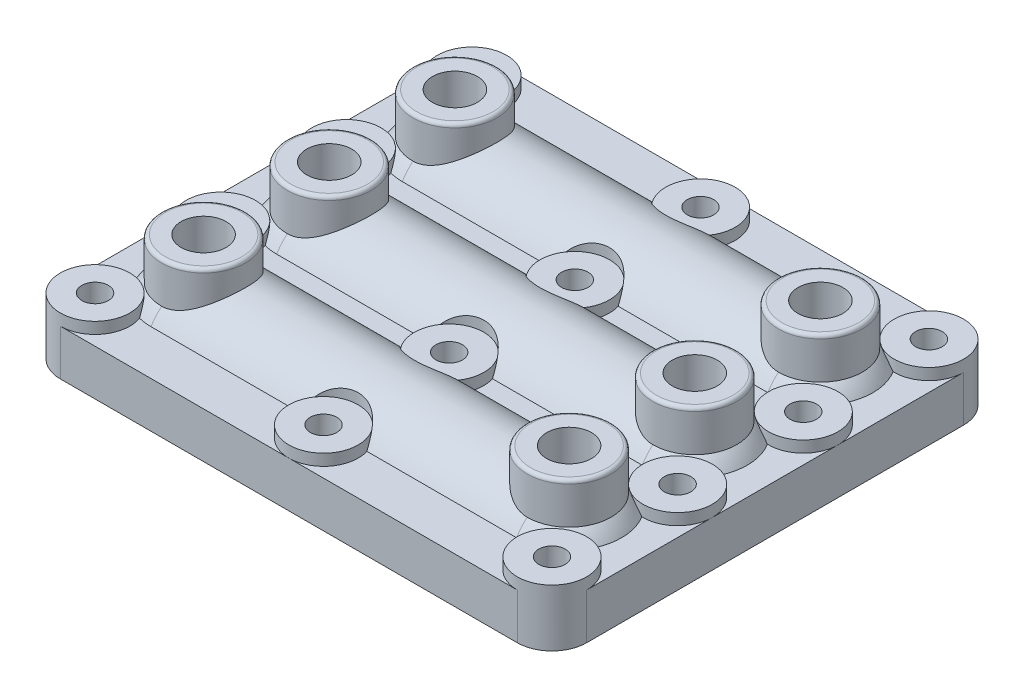
SolidWorks part; units mm, degrees
ref_plane "Front" through (0, 0, 0) normal (0, 0, 1) x (1, 0, 0)
ref_plane "Top" through (0, 0, 0) normal (0, 1, 0) x (1, 0, 0)
ref_plane "Right" through (0, 0, 0) normal (1, 0, 0) x (0, 0, -1)
sketch "Hole Layout" plane through (0, 0, 0) normal (0, 1, 0) x (1, 0, 0)
  line L0 (-31.75, 8.7312) -> (31.75, 8.7312) construction
  line L1 (0, 26.1937) -> (0, -26.1937) construction
  line L2 (-31.75, 26.1937) -> (31.75, 26.1937) construction
  line L3 (-31.75, -8.7313) -> (31.75, -8.7312) construction
  line L4 (-31.75, -26.1937) -> (31.75, -26.1937) construction
  circle A0 centre (-31.75, 26.1937) radius 3.175
  circle A1 centre (0, 26.1937) radius 3.175
  circle A2 centre (31.75, 26.1937) radius 3.175
  circle A3 centre (-31.75, 8.7312) radius 3.175
  circle A4 centre (0, 8.7312) radius 3.175
  circle A5 centre (31.75, 8.7312) radius 3.175
  circle A6 centre (-31.75, -8.7313) radius 3.175
  circle A7 centre (0, -8.7312) radius 3.175
  circle A8 centre (31.75, -8.7312) radius 3.175
  circle A9 centre (-31.75, -26.1937) radius 3.175
  circle A10 centre (0, -26.1937) radius 3.175
  circle A11 centre (31.75, -26.1937) radius 3.175
  circle A12 centre (-31.75, 26.1937) radius 2.413
  point P5 (0, 0)
  point P8 (0, 26.1937)
  point P10 (0, 8.7312)
  point P11 (0, -8.7312)
  dimension "D8" = 6.35
  dimension "D9" = 6.35
  dimension "D10" = 6.35
  dimension "D11" = 6.35
  dimension "D12" = 6.35
  dimension "D13" = 6.35
  dimension "D14" = 6.35
  dimension "D15" = 6.35
  dimension "D16" = 6.35
  dimension "D17" = 6.35
  dimension "D18" = 6.35
  dimension "D19" = 6.35
  dimension "D20" = 4.826
  dimension "D1" = 63.5
  dimension "D2" = 52.3875
  dimension "D3" = 63.5
  dimension "D4" = 8.7312
  dimension "D5" = 63.5
  dimension "D6" = 8.7312
  dimension "D7" = 63.5
sketch "Gas Layout" plane through (0, 0, 0) normal (0, 1, 0) x (1, 0, 0)
  line L0 (-25.4, 0) -> (25.4, 0) construction
  line L1 (-25.4, 17.4625) -> (25.4, 17.4625) construction
  line L2 (-25.4, -17.4625) -> (25.4, -17.4625) construction
  line L3 (0, 17.4625) -> (0, -17.4625) construction
  circle A0 centre (-25.4, 17.4625) radius 1.5875
  circle A1 centre (-25.4, 0) radius 1.5875
  circle A2 centre (-25.4, -17.4625) radius 1.5875
  circle A3 centre (25.4, 17.4625) radius 1.5875
  circle A4 centre (25.4, 0) radius 1.5875
  circle A5 centre (25.4, -17.4625) radius 1.5875
  point P5 (0, 17.4625)
  point P18 (0, 0)
  point P19 (0, -17.4625)
  dimension "D4" = 3.175
  dimension "D5" = 3.175
  dimension "D6" = 3.175
  dimension "D7" = 3.175
  dimension "D8" = 3.175
  dimension "D9" = 3.175
  dimension "D1" = 50.8
  dimension "D2" = 50.8
  dimension "D3" = 50.8
  dimension "D10" = 34.925
sketch "Gas Channel" plane through (0, 0, 0) normal (0, 1, 0) x (1, 0, 0)
  line L0 (-19.05, 17.4625) -> (19.05, 17.4625) construction
  line L1 (19.05, 15.2174) -> (19.05, 19.7076) construction
  line L2 (-25.4, 17.4625) -> (25.4, 17.4625) construction
  line L3 (-19.05, 19.7076) -> (19.05, 19.7076)
  line L4 (-19.05, 15.2174) -> (19.05, 15.2174)
  arc A0 (-19.05, 19.7076) -> (-19.05, 15.2174) centre (-19.05, 17.4625) ccw
  arc A1 (19.05, 15.2174) -> (19.05, 19.7076) centre (19.05, 17.4625) ccw
  point P5 (0, 17.4625)
  dimension "D1" = 19.05
  dimension "D2" = 4.4901
sketch "Perimeter" plane through (0, 0, 0) normal (0, 1, 0) x (1, 0, 0)
  line L0 (-31.75, 31.0197) -> (31.75, 31.0197)
  line L1 (-36.576, 26.1937) -> (-36.576, -26.1937)
  line L2 (36.576, 26.1937) -> (36.576, -26.1937)
  line L3 (-31.75, -31.0197) -> (31.75, -31.0197)
  circle A0 centre (-31.75, 26.1937) radius 4.826
  circle A1 centre (31.75, 26.1937) radius 4.826
  circle A2 centre (-31.75, -26.1937) radius 4.826
  circle A3 centre (31.75, -26.1937) radius 4.826
  dimension "D1" = 9.652
  dimension "D2" = 9.652
  dimension "D3" = 9.652
  dimension "D4" = 9.652
sketch "Footprint A" plane through (0, 0, 0) normal (0, 1, 0) x (1, 0, 0)
  line L0 (-31.75, 8.7312) -> (31.75, 8.7312) construction
  circle A0 centre (-31.75, 26.1937) radius 3.302
  circle A1 centre (0, 26.1937) radius 3.302
  circle A2 centre (31.75, 26.1937) radius 3.302
  circle A3 centre (-31.75, 8.7312) radius 3.302
  circle A4 centre (0, 8.7312) radius 3.302
  circle A5 centre (31.75, 8.7312) radius 3.302
  circle A6 centre (-31.75, -8.7313) radius 3.302
  circle A7 centre (0, -8.7312) radius 3.302
  circle A8 centre (31.75, -8.7312) radius 3.302
  circle A9 centre (-31.75, -26.1937) radius 3.302
  circle A10 centre (0, -26.1937) radius 3.302
  circle A11 centre (31.75, -26.1937) radius 3.302
  dimension "D1" = 6.604
  dimension "D2" = 6.604
  dimension "D3" = 6.604
  dimension "D4" = 6.604
  dimension "D5" = 6.604
  dimension "D6" = 6.604
  dimension "D7" = 6.604
  dimension "D8" = 6.604
  dimension "D9" = 6.604
  dimension "D10" = 6.604
  dimension "D11" = 6.604
  dimension "D12" = 6.604
sketch "Footprint B" plane through (0, 0, 0) normal (0, 1, 0) x (1, 0, 0)
  line L0 (-31.75, 31.0197) -> (31.75, 31.0197)
  line L1 (-36.576, 26.1937) -> (-36.576, -26.1937)
  line L2 (36.576, 26.1937) -> (36.576, -26.1937)
  line L3 (-31.75, -31.0197) -> (31.75, -31.0197)
  arc A0 (-31.75, 31.0197) -> (-36.576, 26.1937) centre (-31.75, 26.1937) ccw
  arc A6 (36.576, 26.1937) -> (31.75, 31.0197) centre (31.75, 26.1937) ccw
  arc A12 (-36.576, -26.1937) -> (-31.75, -31.0197) centre (-31.75, -26.1937) ccw
  arc A13 (31.75, -31.0197) -> (36.576, -26.1937) centre (31.75, -26.1937) ccw
  dimension "D1" = 9.652
  dimension "D2" = 9.652
  dimension "D3" = 9.652
extrude "Boss-Extrude1" add sketch "Footprint B" along normal blind 1.5875 contours L3 A13 L2 A6 L0 A0 L1 A12 region at (0, 0, 0)
ref_plane "Plane3" through (0, 1.5875, 0) normal (0, 1, 0) x (1, 0, 0)
sketch "Main Body A" plane through (0, 1.5875, 0) normal (0, 1, 0) x (1, 0, 0)
  line L0 (-36.576, 26.1937) -> (-36.576, -26.1937)
  line L1 (-31.75, -31.0197) -> (31.75, -31.0197)
  line L2 (36.576, -26.1937) -> (36.576, 26.1937)
  line L3 (31.75, 31.0198) -> (-31.75, 31.0197)
  line L4 (-31.75, 31.0197) -> (31.75, 31.0197) construction
  line L5 (-31.75, -31.0197) -> (31.75, -31.0197) construction
  line L6 (36.576, 26.1937) -> (36.576, -26.1937) construction
  line L7 (-36.576, 26.1937) -> (-36.576, -26.1937) construction
  arc A0 (-36.576, -26.1937) -> (-31.75, -31.0197) centre (-31.75, -26.1937) ccw
  arc A1 (31.75, -31.0197) -> (36.576, -26.1937) centre (31.75, -26.1937) ccw
  arc A2 (36.576, 26.1937) -> (31.75, 31.0198) centre (31.75, 26.1937) ccw
  arc A3 (-36.576, 26.1937) -> (-31.75, 31.0197) centre (-31.75, 26.1937) cw
  dimension "D1" = 4.826
extrude "Boss-Extrude2" add sketch "Main Body A" along normal blind 4.7625
sketch "Inlet/outlet posts" plane through (0, 0, 0) normal (0, 1, 0) x (1, 0, 0)
  circle A0 centre (25.4, 17.4625) radius 5.842
  circle A2 centre (25.4, 0) radius 5.842
  circle A3 centre (25.4, -17.4625) radius 5.842
  circle A4 centre (-25.4, -17.4625) radius 5.842
  circle A5 centre (-25.4, 0) radius 5.842
  circle A6 centre (-25.4, 17.4625) radius 5.842
  dimension "D1" = 11.684
  dimension "D2" = 11.684
  dimension "D3" = 11.684
  dimension "D4" = 11.684
  dimension "D5" = 11.684
  dimension "D6" = 11.684
extrude "Boss-Extrude4" add sketch "Inlet/outlet posts" along normal blind 13.7795
sketch "Sketch21" plane through (0, 1.5875, 0) normal (0, 1, 0) x (-1, 0, 0)
  line L0 (-41.0473, -17.4625) -> (41.0473, -17.4625) construction
  line L1 (0, -17.4625) -> (0, 0) construction
  line L2 (25.4, -17.4625) -> (-25.4, -17.4625) construction
  line L3 (25.4, -17.4625) -> (-25.4, -17.4625) construction
  line L5 (25.4, -8.7312) -> (-25.4, -8.7313)
  line L6 (34.1313, -17.4625) -> (-34.1313, -17.4625)
  arc A0 (34.1313, -17.4625) -> (25.4, -8.7312) centre (25.4, -17.4625) ccw
  arc A1 (-25.4, -8.7313) -> (-34.1313, -17.4625) centre (-25.4, -17.4625) ccw
  point P9 (0, -17.4625)
  point P12 (0, -17.4625)
  point P18 (0, -8.7312)
  point P19 (0, -8.7312)
revolve "Revolve2" add sketch "Sketch21" angle 180 about L0
pattern_linear "LPattern1" count 3 spacing 17.4625 along (0, 0, 1) of "Revolve2"
sketch "Sketch22" plane through (0, 6.35, 0) normal (0, 1, 0) x (1, 0, 0)
  circle A0 centre (-31.75, 26.1937) radius 4.826
  circle A1 centre (-31.75, 8.7312) radius 4.826
  circle A2 centre (-31.75, -8.7313) radius 4.826
  circle A3 centre (-31.75, -26.1937) radius 4.826
  circle A4 centre (0, -26.1938) radius 4.826
  circle A5 centre (0, -8.7312) radius 4.826
  circle A6 centre (0, 8.7312) radius 4.826
  circle A7 centre (0, 26.1937) radius 4.826
  circle A8 centre (31.75, 26.1937) radius 4.826
  circle A9 centre (31.75, 8.7312) radius 4.826
  circle A10 centre (31.75, -8.7312) radius 4.826
  circle A11 centre (31.75, -26.1937) radius 4.826
  dimension "D1" = 9.652
extrude "Boss-Extrude5" add sketch "Sketch22" along normal blind 1.5875
sketch "Sketch23" plane through (0, 7.9375, 0) normal (0, 1, 0) x (1, 0, 0)
  circle A0 centre (0, -26.1937) radius 4.826
  circle A1 centre (0, -8.7312) radius 4.826
  circle A2 centre (0, 8.7312) radius 4.826
  circle A3 centre (0, 26.1937) radius 4.826
extrude "Cut-Extrude3" cut sketch "Sketch23" along normal through all
sketch "Sketch24" plane through (0, 7.9375, 0) normal (0, 1, 0) x (1, 0, 0)
  circle A0 centre (-31.75, 26.1937) radius 1.8415
  circle A1 centre (-31.75, 8.7312) radius 1.8415
  circle A2 centre (-31.75, -8.7313) radius 1.8415
  circle A3 centre (-31.75, -26.1937) radius 1.8415
  circle A4 centre (0, 26.1937) radius 1.8415
  circle A5 centre (0, 8.7312) radius 1.8415
  circle A6 centre (0, -8.7313) radius 1.8415
  circle A7 centre (0, -26.1937) radius 1.8415
  circle A8 centre (31.75, 26.1937) radius 1.8415
  circle A9 centre (31.75, 8.7312) radius 1.8415
  circle A10 centre (31.75, -8.7312) radius 1.8415
  circle A11 centre (31.75, -26.1937) radius 1.8415
  dimension "D1" = 3.683
extrude "Cut-Extrude4" cut sketch "Sketch24" against normal through all
sketch "Sketch19" plane through (0, 13.7795, 0) normal (0, 1, 0) x (1, 0, 0)
  circle A0 centre (-25.4, 17.4625) radius 3.1242
  circle A1 centre (-25.4, 0) radius 3.1242
  circle A2 centre (-25.4, -17.4625) radius 3.1242
  circle A3 centre (25.4, 17.4625) radius 3.1242
  circle A4 centre (25.4, 0) radius 3.1242
  circle A5 centre (25.4, -17.4625) radius 3.1242
  dimension "D1" = 6.2484
  dimension "D2" = 6.2484
  dimension "D3" = 6.2484
  dimension "D4" = 6.2484
  dimension "D5" = 6.2484
  dimension "D6" = 6.2484
extrude "Cut-Extrude2" cut sketch "Sketch19" against normal blind 5.842
extrude "Cut-Extrude1" cut sketch "Gas Channel" along normal blind 0.9322 contours A1 L3 A0 L4
sketch "Sketch13" plane through (0, 0.9322, 0) normal (0, -1, 0) x (1, 0, 0)
  line L0 (-22.0111, -17.4625) -> (21.8692, -17.4625) construction
  line L1 (-25.4, -17.4625) -> (25.4, -17.4625) construction
  line L2 (-19.05, 0) -> (19.05, 0) construction
  line L3 (-19.05, 2.2451) -> (19.05, 2.2451)
  line L4 (-19.05, -2.2451) -> (19.05, -2.2451)
  line L5 (-19.05, -19.7076) -> (19.05, -19.7076) construction
  line L6 (-19.05, -19.7076) -> (19.05, -19.7076)
  line L7 (-21.2951, -17.4625) -> (21.2951, -17.4625)
  arc A0 (-19.05, 2.2451) -> (-19.05, -2.2451) centre (-19.05, 0) ccw
  arc A1 (19.05, -2.2451) -> (19.05, 2.2451) centre (19.05, 0) ccw
  arc A3 (19.05, -19.7076) -> (19.05, -15.2174) centre (19.05, -17.4625) ccw construction
  arc A4 (-19.05, -15.2174) -> (-19.05, -19.7076) centre (-19.05, -17.4625) ccw construction
  arc A5 (19.05, -19.7076) -> (21.2951, -17.4625) centre (19.05, -17.4625) ccw
  arc A6 (-21.2951, -17.4625) -> (-19.05, -19.7076) centre (-19.05, -17.4625) ccw
  point P6 (0, 0)
revolve "Cut-Revolve7" cut sketch "Sketch13" angle 180 about L0
ref_axis "Axis1" through (0, 0, -37.8212) along (0, 0, 1)
pattern_linear "LPattern6" count 3 spacing 17.4625 along (0, 0, 1) of "Cut-Extrude1", "Cut-Revolve7"
ref_plane "Plane1" through (19.05, 0, 0) normal (1, 0, 0) x (0, 0, -1)
sketch "Sketch14" plane through (19.05, 0, 0) normal (1, 0, 0) x (0, 0, -1)
  line L0 (26.1937, 0) -> (-26.1937, 0) construction
  line L3 (15.2174, 0.9322) -> (19.7076, 0.9322) construction
  line L4 (17.4625, -0.3456) -> (17.4625, 2.2099) construction
  line L5 (12.9152, 7.9375) -> (22.0672, 7.9375) construction
  circle A0 centre (17.4625, 1.5875) radius 1.5875
  point P8 (17.4625, 0.9322)
  point P9 (17.4625, 0.9322)
  dimension "D1" = 3.175
  dimension "D2" = 6.35
ref_plane "Plane2" through (0, 7.9375, 0) normal (0, 1, 0) x (1, 0, 0)
revolve "Cut-Revolve8" cut sketch "Sketch14" angle 90 about L5 reverse direction yes
pattern_linear "LPattern7" count 3 spacing 17.4625 along (0, 0, 1) of "Cut-Revolve8"
mirror "Mirror1" about plane through (0, 0, 0) normal (1, 0, 0) of "LPattern7"
fillet "Fillet1" radius 0.508 6 edges at (25.4, 13.7795, 23.3045) (-25.4, 13.7795, 23.3045) (-25.4, 13.7795, 5.842) (25.4, 13.7795, 5.842) (25.4, 13.7795, -11.6205) (-25.4, 13.7795, -11.6205)
sketch "Sketch25" plane through (0, 0, 0) normal (0, -1, 0) x (1, 0, 0)
  line L0 (-19.05, -15.2174) -> (19.05, -15.2174) construction
  line L1 (-19.05, -15.2174) -> (19.05, -15.2174)
  line L2 (0, -11.9062) -> (0, -15.2174) construction
  line L3 (0, -26.1937) -> (0, 26.1937) construction
  line L4 (-23.5306, -17.4625) -> (23.5306, -17.4625) construction
  line L5 (-25.4, -17.4625) -> (25.4, -17.4625) construction
  line L6 (-23.5306, -12.6728) -> (23.5306, -12.6728)
  line L7 (-23.5306, -22.2522) -> (23.5306, -22.2522)
  circle A0 centre (0, -8.7312) radius 3.175 construction
  arc A1 (-23.5306, -12.6728) -> (-23.5306, -22.2522) centre (-23.5306, -17.4625) ccw
  arc A2 (23.5306, -22.2522) -> (23.5306, -12.6728) centre (23.5306, -17.4625) ccw
  point P13 (0, -17.4625)
  point P19 (0, -13.5618)
  point P20 (0, -12.6728)
  dimension "D1" = 0.889
  dimension "D2" = 23.5306
  dimension "D3" = 4.7897
sketch "Sketch27" plane through (0, 0, 0) normal (1, 0, 0) x (0, 0, -1)
  line L1 (13.5618, -0.4987) -> (12.6728, -0.4987)
  line L2 (12.6728, -0.4987) -> (12.6728, 0.3903)
  line L3 (12.6728, 0) -> (12.6728, 2.8803) construction
  line L4 (26.1937, 0) -> (-26.1937, 0) construction
  arc A0 (13.5618, -0.4987) -> (12.6728, 0.3903) centre (13.5618, 0.3903) ccw
  dimension "D1" = 1.778
sweep "Cut-Sweep1" cut profiles "Sketch27" path "Sketch25"
pattern_linear "LPattern8" count 3 spacing 17.4625 along (0, 0, 1) of "Cut-Sweep1"
equation "\"SD\"= .25'Swage Footprint Diameter"
equation "\"D8@Hole Layout\" = \"SD\""
equation "\"D9@Hole Layout\" = \"SD\""
equation "\"D10@Hole Layout\" = \"SD\""
equation "\"D11@Hole Layout\" = \"SD\""
equation "\"D12@Hole Layout\" = \"SD\""
equation "\"D13@Hole Layout\" = \"SD\""
equation "\"D14@Hole Layout\" = \"SD\""
equation "\"D15@Hole Layout\" = \"SD\""
equation "\"D16@Hole Layout\" = \"SD\""
equation "\"D17@Hole Layout\" = \"SD\""
equation "\"D18@Hole Layout\" = \"SD\""
equation "\"D19@Hole Layout\" = \"SD\""
equation "\"Landing_1\"= .38'6-32 washer Landing Diameter"
equation "\"D1@Perimeter\"= \"Landing_1\""
equation "\"D2@Perimeter\"=\"Landing_1\""
equation "\"D3@Perimeter\"=\"Landing_1\""
equation "\"C_1\"= .01'Swage Clearance Diameter"
equation "\"D1@Footprint A\" = \"SD\" + \"C_1\""
equation "\"D2@Footprint A\" = \"SD\" + \"C_1\""
equation "\"D3@Footprint A\" = \"SD\" + \"C_1\""
equation "\"D4@Footprint A\" = \"SD\" + \"C_1\""
equation "\"D5@Footprint A\" = \"SD\" + \"C_1\""
equation "\"D6@Footprint A\" = \"SD\" + \"C_1\""
equation "\"D7@Footprint A\" = \"SD\" + \"C_1\""
equation "\"D8@Footprint A\" = \"SD\" + \"C_1\""
equation "\"D9@Footprint A\" = \"SD\" + \"C_1\""
equation "\"D10@Footprint A\" = \"SD\" + \"C_1\""
equation "\"D11@Footprint A\" = \"SD\" + \"C_1\""
equation "\"D12@Footprint A\"= \"SD\" + \"C_1\""
equation "\"D1@Main Body A\"= \"Landing_1\" / 2"
equation "\"OD\" = 1.55'O-Ring OD"
equation "\"W\"= .07'O-Ring Width"
equation "\"D2@Sketch25\"= \"OL\"/2 - 0.1886"
equation "\"OL\"= 2.23'Deformed O-Ring Long Dimension"
